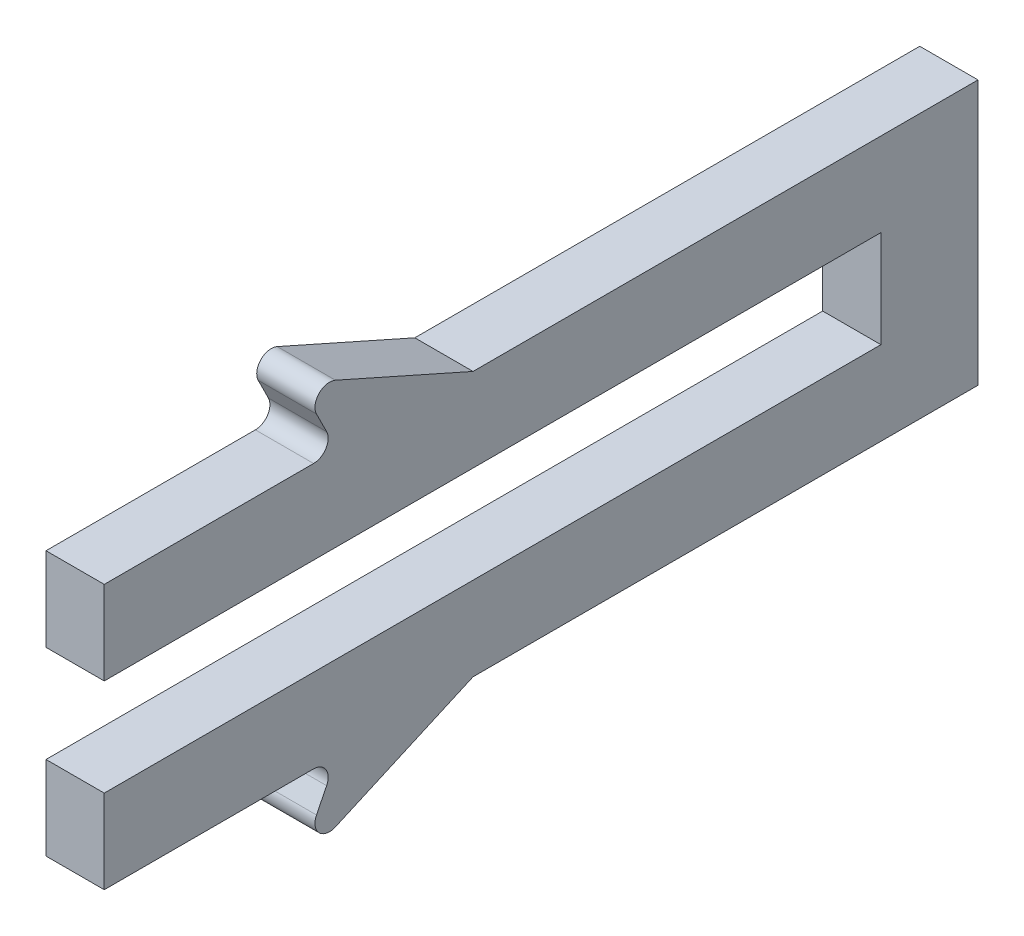
SolidWorks part; units mm, degrees
material "Custom Plastic"
ref_plane "Front Plane" through (0, 0, 0) normal (0, 0, 1) x (1, 0, 0)
ref_plane "Top Plane" through (0, 0, 0) normal (0, 1, 0) x (1, 0, 0)
ref_plane "Right Plane" through (0, 0, 0) normal (1, 0, 0) x (0, 0, -1)
sketch "Sketch2" plane through (0, 0, 0) normal (1, 0, 0) x (0, 0, -1)
  line L0 (-20.9136, -4.3885) -> (-8.9196, -4.3885)
  line L1 (24.0864, -4.3885) -> (24.0864, -18.0092)
  line L2 (24.0864, -18.0092) -> (-1.9196, -18.0092)
  line L3 (-20.9136, -18.0092) -> (-20.9136, -13.6989)
  line L4 (-20.9136, -13.6989) -> (19.0864, -13.6989)
  line L5 (19.0864, -13.6989) -> (19.0864, -8.6989)
  line L6 (19.0864, -8.6989) -> (-20.9136, -8.6989)
  line L7 (-20.9136, -8.6989) -> (-20.9136, -4.3885)
  line L8 (-1.9196, -4.3885) -> (-10.9136, -0.3885)
  line L9 (-10.9136, -0.3885) -> (-8.9196, -4.3885)
  line L10 (24.0864, -11.1989) -> (-19.6352, -11.1989) construction
  line L11 (-10.9136, -22.0092) -> (-8.9196, -18.0092)
  line L12 (-1.9196, -18.0092) -> (-10.9136, -22.0092)
  line L13 (-1.9196, -4.3885) -> (24.0864, -4.3885)
  line L14 (-8.9196, -18.0092) -> (-20.9136, -18.0092)
  dimension "D1" = 5
  dimension "D2" = 40
  dimension "D3" = 45
  dimension "D4" = 4
  dimension "D5" = 7
  dimension "D6" = 10
extrude "Boss-Extrude1" add sketch "Sketch2" along normal blind 3
fillet "Fillet1" radius 0.75 4 edges at (1.5, -22.0092, 10.9136) (1.5, -18.0092, 8.9196) (1.5, -4.3885, 8.9196) (1.5, -0.3885, 10.9136)
